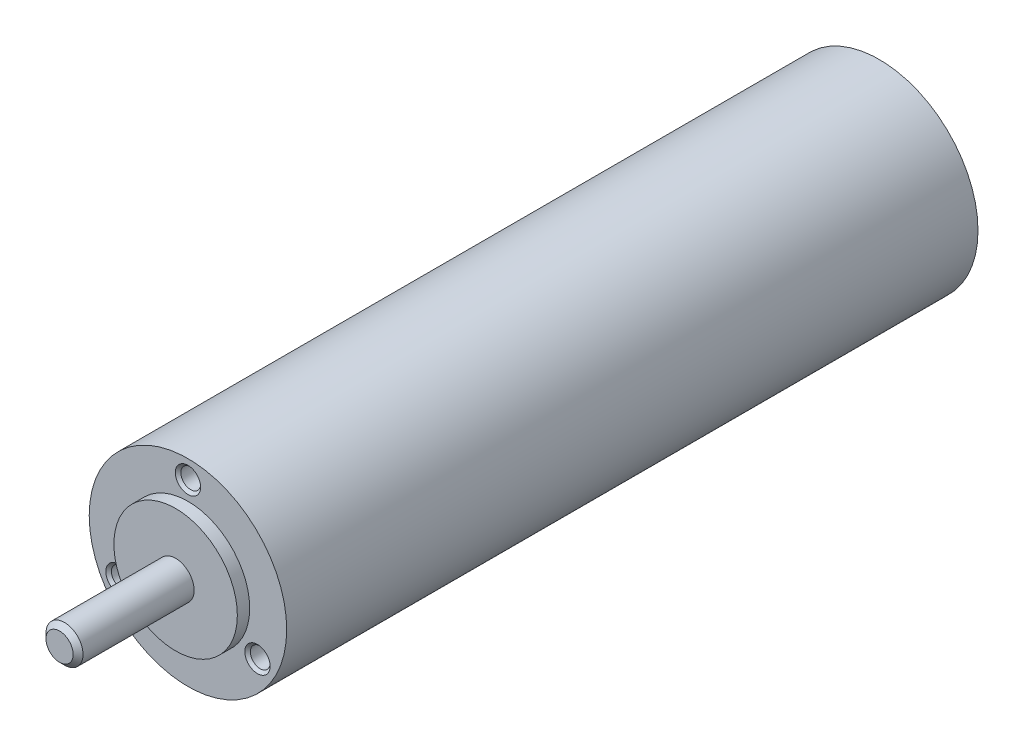
SolidWorks part; units mm, degrees
material "Нержавеющая сталь (ферритная)"
ref_plane "Спереди" through (0, 0, 0) normal (0, 0, 1) x (1, 0, 0)
ref_plane "Сверху" through (0, 0, 0) normal (0, 1, 0) x (1, 0, 0)
ref_plane "Справа" through (0, 0, 0) normal (1, 0, 0) x (0, 0, -1)
sketch "Эскиз1" plane through (0, 0, 0) normal (1, 0, 0) x (0, 0, -1)
  line L0 (0, 0) -> (66.4, 0) construction
  line L1 (0, 0) -> (0, -1.5)
  line L2 (0, -1.5) -> (9.4, -1.5)
  line L3 (9.4, -1.5) -> (9.4, -5)
  line L4 (9.4, -5) -> (10.4, -5)
  line L5 (10.4, -5) -> (10.4, -8)
  line L6 (10.4, -8) -> (66.4, -8)
  line L7 (66.4, -8) -> (66.4, 0)
  line L8 (0, 0) -> (66.4, 0)
  dimension "D1" = 3
  dimension "D2" = 10
  dimension "D3" = 16
  dimension "D4" = 56
  dimension "D5" = 10.4
  dimension "D6" = 1
revolve "Повернуть1" add sketch "Эскиз1" angle 360 about L0
chamfer "Фаска1" distance 0.4 1 edges at (1.5, 0, 0)
hole_wizard "Отверстие обработанное метчиком M2x0.41" positions "Эскиз4" profile "Эскиз5" tap size "M2x0.4" standard "Ansi Metric"
sketch "Эскиз4" plane through (0, 0, -10.4) normal (0, 0, 1) x (1, 0, 0)
  circle A0 centre (0, 0) radius 6.5 construction
  point P0 (0, 6.5)
  dimension "D1" = 13
sketch "Эскиз5" plane through (0, 6.5, -10.4) normal (1, 0, 0) x (0, -1, 0)
  line L0 (0, 0) -> (0, 4.4807)
  line L1 (0, 4.4807) -> (0.8, 4)
  line L2 (0.8, 4) -> (0.8, 0.225)
  line L3 (0.8, 0.225) -> (1.025, 0)
  line L5 (1.025, 0) -> (0, 0)
  line L6 (-0.8, 0.225) -> (-1.025, 0) construction
  line L10 (0, 4.4807) -> (-0.8, 4) construction
  line L11 (0, -6.35) -> (0, 107.95) construction
  dimension "Диаметр сверла" = 1.6
  dimension "Глубина сверла" = 4
  dimension "Диаметр передней зенковки" = 2.05
  dimension "Угол передней зенковки" = 90
  dimension "Угол заточки сверла" = 118
cosmetic thread "Отверстие резьбы1" parameters "D1"=3.5, "D2"=2
pattern_circular "Круговой массив1" count 3 over 360 about axis through (0, 0, 0) along (0, 0, 1) of "Отверстие обработанное метчиком M2x0.41"
